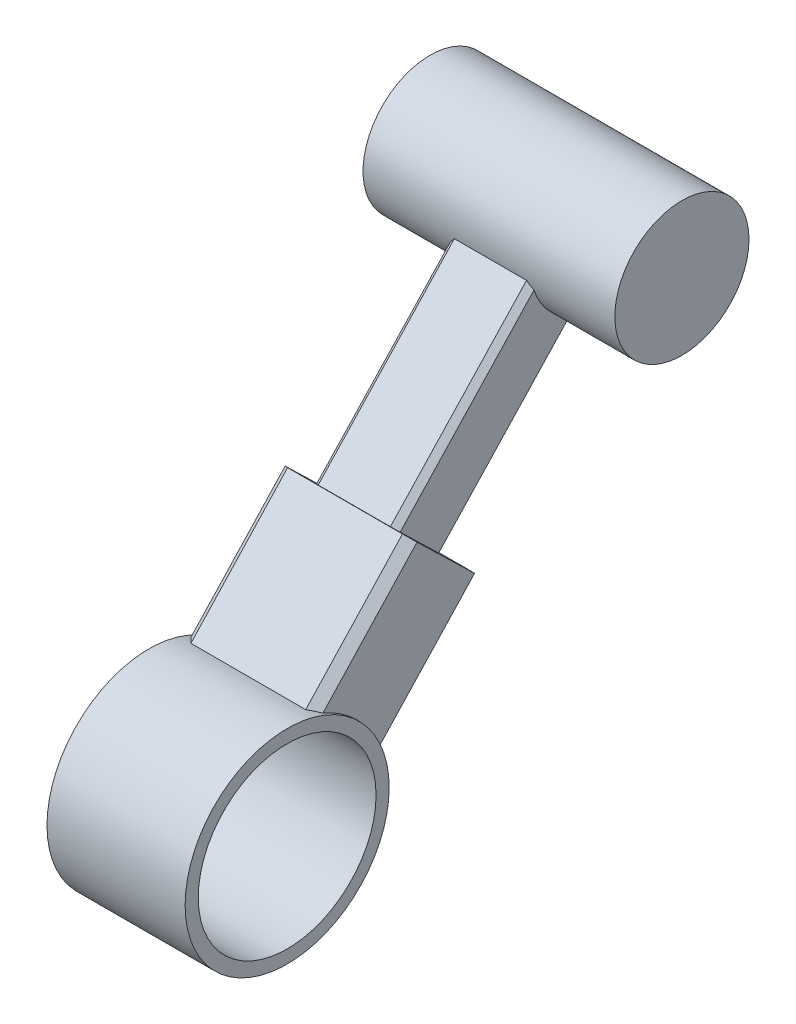
SolidWorks part; units mm, degrees
ref_plane "Front Plane" through (0, 0, 0) normal (0, 0, 1) x (1, 0, 0)
ref_plane "Top Plane" through (0, 0, 0) normal (0, 1, 0) x (1, 0, 0)
ref_plane "Right Plane" through (0, 0, 0) normal (1, 0, 0) x (0, 0, -1)
sketch "Sketch1" plane through (0, 0, 0) normal (1, 0, 0) x (0, 0, -1)
  line L0 (177.0385, 548.1698) -> (190.0817, 534.2804)
  line L1 (190.0817, 534.2804) -> (128.192, 468.2162)
  line L2 (128.192, 468.2162) -> (114.7191, 481.6892)
  line L3 (114.7191, 481.6892) -> (177.0385, 548.1698)
extrude "Boss-Extrude1" add sketch "Sketch1" along normal blind 12.2387 and the other way blind 12.2387
sketch "Sketch2" plane through (0, 0, 0) normal (1, 0, 0) x (0, 0, -1)
  line L0 (123.9848, 497.1245) -> (144.418, 477.3231)
  line L1 (144.418, 477.3231) -> (97.5909, 427.1071)
  line L2 (97.5909, 427.1071) -> (77.7898, 447.5401)
  line L3 (77.7898, 447.5401) -> (123.9848, 497.1245)
extrude "Boss-Extrude2" add sketch "Sketch2" along normal blind 19.3111 and the other way blind 19.3111
sketch "Sketch3" plane through (0, 0, 0) normal (1, 0, 0) x (0, 0, -1)
  circle A0 centre (86.7984, 438.1663) radius 29.8912
  point P2 (71.6504, 463.9348)
extrude "Boss-Extrude3" add sketch "Sketch3" along normal blind 20.2367 and the other way blind 20.2367
sketch "Sketch4" plane through (0, 0, 0) normal (1, 0, 0) x (0, 0, -1)
  circle A0 centre (185.8117, 541.1889) radius 19.6561
  point P2 (168.7749, 550.9925)
extrude "Boss-Extrude4" add sketch "Sketch4" along normal blind 36.8869 and the other way blind 36.8869
sketch "Sketch5" plane through (20.2367, 0, 0) normal (1, 0, 0) x (0, 0, -1)
  circle A0 centre (86.7984, 438.1663) radius 26.0502
  point P3 (86.7984, 464.2165)
extrude "Cut-Extrude1" cut sketch "Sketch5" against normal through all
chamfer "Chamfer1" distance 1.665 4 edges at (-12.2387, 501.9532, -159.7972) (-12.2387, 515.7581, -146.6555) (12.2387, 501.9532, -159.7972) (12.2387, 515.7581, -146.6555)
chamfer "Chamfer2" distance 2.4869 4 edges at (-19.3111, 461.8416, -129.9813) (19.3111, 461.8416, -129.9813) (-19.3111, 481.9199, -109.8195) (19.3111, 481.9199, -109.8195)
